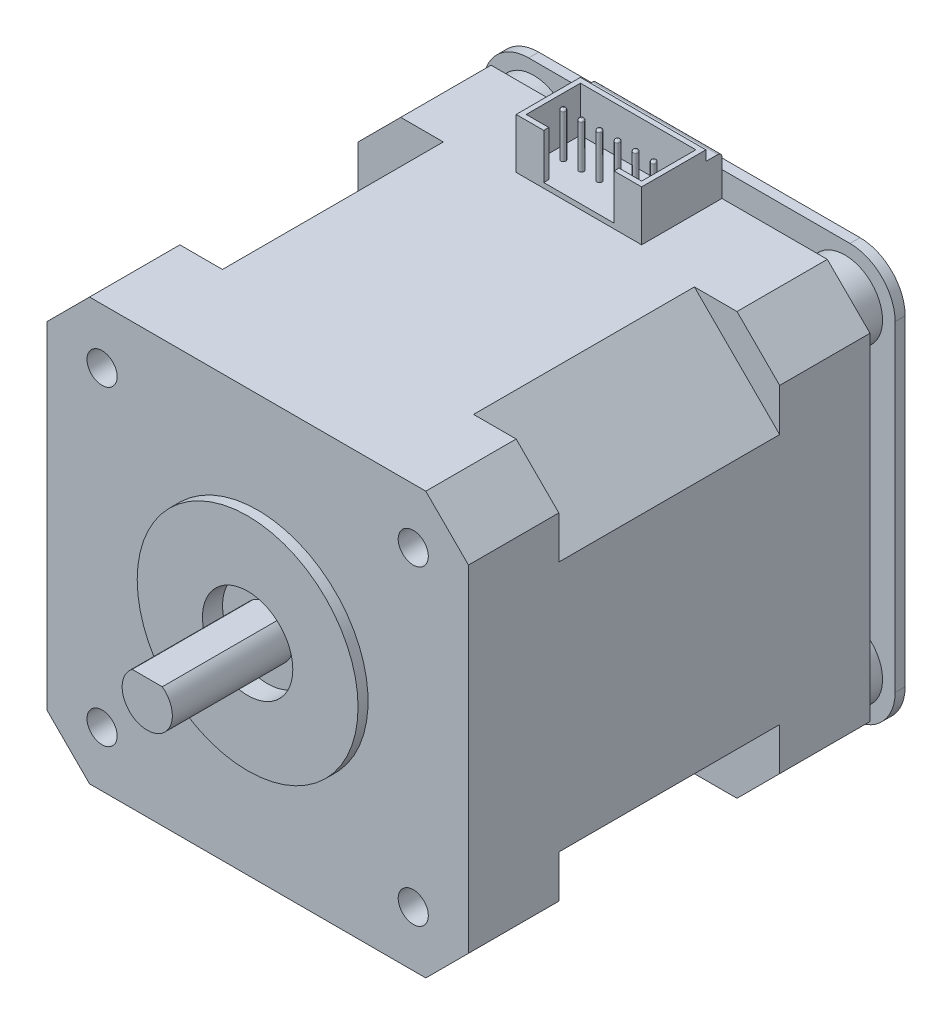
SolidWorks part; units mm, degrees
ref_plane "前视基准面" through (0, 0, 0) normal (0, 0, 1) x (1, 0, 0)
ref_plane "上视基准面" through (0, 0, 0) normal (0, 1, 0) x (1, 0, 0)
ref_plane "右视基准面" through (0, 0, 0) normal (1, 0, 0) x (0, 0, -1)
other "Configuration Table"
sketch "草图1" plane through (0, 0, 0) normal (0, 0, 1) x (1, 0, 0)
  line L0 (0, 0) -> (0, 21) construction
  line L1 (21, 16.75) -> (21, -16.75)
  line L2 (-16.75, 21) -> (16.75, 21)
  line L3 (16.75, -21) -> (-16.75, -21)
  line L4 (-21, -16.75) -> (-21, 16.75)
  line L5 (16.75, 21) -> (21, 16.75)
  line L6 (21, -16.75) -> (16.75, -21)
  line L7 (-16.75, -21) -> (-21, -16.75)
  line L8 (-21, 16.75) -> (-16.75, 21)
  point P2 (0, 0)
  point P3 (0, 21)
  point P4 (0, 0)
  point P10 (-16.7329, -21.7575)
  point P15 (0, 0)
  dimension "D1" = 21
  dimension "D2" = 33.5
  dimension "D3" = 4
extrude "凸台-拉伸1" add sketch "草图1" along normal mid plane 40 contours L2 L5 L1 L6 L3 L7 L4 L8
sketch "草图3" plane through (0, 0, 20) normal (0, 0, 1) x (1, 0, 0)
  circle A0 centre (0, 0) radius 11
  dimension "D1" = 22
extrude "凸台-拉伸2" add sketch "草图3" along normal mid plane 2
sketch "草图4" plane through (0, 0, 21) normal (0, 0, 1) x (1, 0, 0)
  circle A0 centre (0, 0) radius 4.5
  dimension "D1" = 9
extrude "切除-拉伸1" cut sketch "草图4" against normal blind 2
sketch "草图5" plane through (0, 0, 19) normal (0, 0, 1) x (1, 0, 0)
  circle A0 centre (0, 0) radius 2.5
  dimension "D1" = 5
extrude "凸台-拉伸3" add sketch "草图5" along normal mid plane 24
sketch "草图6" plane through (0, 0, 31) normal (0, 0, 1) x (1, 0, 0)
  line L0 (0, 0) -> (0, 2) construction
  line L1 (-1.5, 2) -> (1.5, 2)
  circle A0 centre (0, 0) radius 2.5 construction
  circle A1 centre (0, 0) radius 2.5
  arc A2 (1.5, 2) -> (-1.5, 2) centre (0, 0) ccw
  point P8 (0, 2)
  dimension "D1" = 2
  dimension "D2" = 0
extrude "切除-拉伸2" cut sketch "草图6" against normal blind 24
sketch "草图7" plane through (0, 0, -20) normal (0, 0, -1) x (-1, 0, 0)
  circle A0 centre (0, 0) radius 3
  dimension "D1" = 6
extrude "切除-拉伸3" cut sketch "草图7" against normal blind 2
sketch "草图8" plane through (0, 0, -18) normal (0, 0, -1) x (-1, 0, 0)
  circle A0 centre (0, 0) radius 1.75
  point P2 (0, 0)
  dimension "D1" = 3.5
extrude "凸台-拉伸4" add sketch "草图8" along normal blind 1
sketch "草图9" plane through (0, 0, 20) normal (0, 0, 1) x (1, 0, 0)
  line L0 (0, 0) -> (15.5, 0) construction
  line L1 (15.5, 0) -> (15.5, 15.5) construction
  circle A0 centre (15.5, 15.5) radius 1.5
  circle A1 centre (15.5, -15.5) radius 1.5
  circle A2 centre (-15.5, -15.5) radius 1.5
  circle A3 centre (-15.5, 15.5) radius 1.5
  point P5 (0, 0)
  point P6 (15.5, -15.5)
  point P14 (0, 0)
  dimension "D3" = 3
  dimension "D1" = 15.5
  dimension "D2" = 15.5
  dimension "D4" = 4
extrude "切除-拉伸4" cut sketch "草图9" against normal blind 5
sketch "草图12" plane through (0, 0, -20) normal (0, 0, -1) x (-1, 0, 0)
  line L0 (0, 0) -> (15.5, 0) construction
  line L1 (15.5, 0) -> (15.5, 15.5) construction
  circle A0 centre (15.5, 15.5) radius 3.75
  circle A1 centre (15.5, -15.5) radius 3.75
  circle A2 centre (-15.5, -15.5) radius 3.75
  circle A3 centre (-15.5, 15.5) radius 3.75
  point P5 (-20.6289, 13.0033)
  point P6 (0, 0)
  point P14 (0, 0)
  dimension "D3" = 7.5
  dimension "D1" = 15.5
  dimension "D2" = 15.5
  dimension "D4" = 4
ref_plane "基准面2" through (16.7537, 16.7537, 0) normal (0.7071, 0.7071, 0) x (0.7071, -0.7071, 0)
sketch "草图13" plane through (16.7537, 16.7537, 0) normal (0.7071, 0.7071, 0) x (0.7071, -0.7071, 0)
  line L0 (0, 11) -> (0, -11) construction
  line L1 (-8, -11) -> (8, -11)
  line L2 (-8, 11) -> (8, 11)
  line L3 (-8, 11) -> (-8, -11)
  line L4 (8, 11) -> (8, -11)
  point P2 (0, 0)
  point P8 (0, 11)
  point P9 (0, -11)
  dimension "D1" = 22
  dimension "D2" = 16
  dimension "D3" = 16
extrude "切除-拉伸5" cut sketch "草图13" along normal through all
ref_axis "基准轴1" through (0, 0, 0) along (0, 0, 1)
pattern_circular "阵列(圆周)1" count 4 over 360 about axis through (0, 0, 0) along (0, 0, 1) of "切除-拉伸5"
extrude "凸台-拉伸5" add sketch "草图12" along normal blind 3
sketch "草图15" plane through (0, 0, -20) normal (0, 0, -1) x (-1, 0, 0)
  line L0 (0, 20.5) -> (0, -20.5) construction
  line L1 (20.5, 0) -> (-20.5, 0) construction
  line L2 (-16, 20.5) -> (16, 20.5)
  line L3 (-16, -20.5) -> (16, -20.5)
  line L4 (20.5, 16) -> (20.5, -16)
  line L5 (-20.5, 16) -> (-20.5, -16)
  arc A0 (-20.5, 16) -> (-16, 20.5) centre (-16, 16) cw
  arc A1 (16, 20.5) -> (20.5, 16) centre (16, 16) cw
  arc A2 (20.5, -16) -> (16, -20.5) centre (16, -16) cw
  arc A3 (-16, -20.5) -> (-20.5, -16) centre (-16, -16) cw
  point P2 (0, 0)
  point P4 (0, 0)
  point P5 (0, 0)
  point P16 (20.5, 0)
  point P17 (-20.5, 0)
  point P24 (0, 20.5)
  point P25 (0, -20.5)
  dimension "D1" = 41
  dimension "D2" = 41
  dimension "D3" = 32
  dimension "D4" = 32
extrude "凸台-拉伸6" add sketch "草图15" along normal blind 1 from offset 3
sketch "草图17" plane through (0, 21, 0) normal (0, 1, 0) x (1, 0, 0)
  line L1 (0, 0) -> (0, 20) construction
  line L2 (-16.75, 20) -> (16.75, 20) construction
  line L3 (-6.25, 20) -> (6.25, 20)
  line L4 (-6.25, 12) -> (6.25, 12)
  line L5 (6.25, 12) -> (6.25, 20)
  line L6 (-6.25, 12) -> (-6.25, 20)
  point P7 (0, 20)
  point P10 (0, 12)
  dimension "D1" = 12.5
  dimension "D2" = 8
extrude "凸台-拉伸7" add sketch "草图17" along normal blind 5
sketch "草图20" plane through (6.25, 0, 0) normal (1, 0, 0) x (0, 0, -1)
  line L0 (20, 26) -> (20, 21) construction
  line L1 (12, 26) -> (20, 26) construction
  line L2 (20, 26) -> (20, 25)
  line L3 (18.4, 26) -> (20, 26)
  line L12 (18.4, 26) -> (18.4, 25)
  line L13 (18.4, 25) -> (20, 25)
  dimension "D1" = 1
  dimension "D2" = 1.6
extrude "切除-拉伸6" cut sketch "草图20" against normal through all
fillet "圆角1" radius 0.4 1 edges at (0, 25, -20)
sketch "草图21" plane through (0, 26, 0) normal (0, 1, 0) x (1, 0, 0)
  line L0 (-6.25, 12) -> (6.25, 12) construction
  line L1 (-6.25, 12) -> (6.25, 12) construction
  line L2 (-5.75, 17.9) -> (5.75, 17.9)
  line L3 (0, 12) -> (0, 17.9) construction
  line L4 (-5.75, 12.5) -> (5.75, 12.5)
  line L6 (5.75, 17.9) -> (5.75, 12.5)
  line L8 (-5.75, 17.9) -> (-5.75, 12.5)
  point P8 (0, 12.5)
  dimension "D1" = 5.9
  dimension "D2" = 11.5
  dimension "D3" = 5.4
extrude "切除-拉伸7" cut sketch "草图21" against normal blind 4.5
sketch "草图22" plane through (0, 26, 0) normal (0, 1, 0) x (1, 0, 0)
  line L0 (-5.75, 12.5) -> (5.75, 12.5) construction
  line L1 (-5.75, 12.5) -> (5.75, 12.5) construction
  line L2 (-3.5, 12.5) -> (-3.5, 12)
  line L3 (-6.25, 12) -> (6.25, 12) construction
  line L4 (0, 12.5) -> (0, 12) construction
  line L5 (3.5, 12.5) -> (3.5, 12)
  line L6 (-6.25, 12) -> (6.25, 12) construction
  line L7 (3.5, 12.5) -> (-3.5, 12.5)
  line L8 (-3.5, 12) -> (3.5, 12)
  dimension "D1" = 3.5
  dimension "D2" = 3.5
extrude "切除-拉伸8" cut sketch "草图22" against normal blind 4.5
sketch "草图23" plane through (0, 0, -24) normal (0, 0, -1) x (-1, 0, 0)
  line L0 (20.5, -16) -> (20.5, 16) construction
  line L1 (20.5, -16) -> (20.5, 16) construction
  line L2 (20.5, 0) -> (14.5, 0) construction
  line L3 (14.5, 11.35) -> (14.5, -11.35)
  line L4 (24.5, 11.35) -> (24.5, -11.35)
  line L5 (14.5, 11.35) -> (24.5, 11.35)
  line L6 (24.5, -11.35) -> (14.5, -11.35)
  point P7 (14.5, 0)
  point P10 (24.5, 0)
  dimension "D1" = 6
  dimension "D2" = 22.7
  dimension "D3" = 4
extrude "凸台-拉伸8" add sketch "草图23" along normal blind 6.5
sketch "草图24" plane through (-24.5, 0, 0) normal (-1, 0, 0) x (0, 0, 1)
  line L0 (-30, 10.85) -> (-30, -10.85)
  line L1 (-30.5, 0) -> (-24.3219, 0) construction
  line L2 (-24.5, 10.85) -> (-24.5, -10.85)
  line L3 (-30, 10.85) -> (-24.5, 10.85)
  line L4 (-24, -11.35) -> (-24, 11.35)
  line L5 (-24, 11.35) -> (-30.5, 11.35)
  line L6 (-30.5, 11.35) -> (-30.5, -11.35)
  line L7 (-30.5, -11.35) -> (-24, -11.35)
  line L10 (-30.5, 11.35) -> (-30.5, -11.35) construction
  line L12 (-30, -10.85) -> (-24.5, -10.85)
  point P11 (-24.5, 0)
  point P12 (-30, 0)
  dimension "D2" = 0.5
  dimension "D3" = 21.7
  dimension "D4" = 5.5
  dimension "D1" = 0
extrude "切除-拉伸9" cut sketch "草图24" against normal blind 8
sketch "草图25" plane through (-24.5, 0, 0) normal (-1, 0, 0) x (0, 0, 1)
  line L0 (-30.5, -11.35) -> (-30.5, 11.35) construction
  line L1 (-30.5, -11.35) -> (-30.5, 11.35) construction
  line L2 (-30.5, 0) -> (-30, 0) construction
  line L3 (-30, 10.85) -> (-30, -10.85) construction
  line L4 (-30, 6.5) -> (-30, -6.5)
  line L5 (-30.5, 6.5) -> (-30.5, -6.5)
  line L6 (-30.5, 6.5) -> (-30, 6.5)
  line L7 (-30, -6.5) -> (-30.5, -6.5)
  point P10 (-30.5, 0)
  point P11 (-30, 0)
  dimension "D1" = 13
extrude "切除-拉伸10" cut sketch "草图25" against normal blind 8
sketch "草图26" plane through (-16.5, 0, 0) normal (-1, 0, 0) x (0, 0, 1)
  line L1 (-30.5, 6.5) -> (-30.5, -6.5) construction
  line L2 (-30.5, 0) -> (-24.5, 0) construction
  line L3 (-24.5, -10.85) -> (-24.5, 10.85) construction
  line L4 (-27.5, 4.3514) -> (-27.5, -4.3514) construction
  circle A0 centre (-27.5, 6.5) radius 0.25
  circle A1 centre (-27.5, 3.9) radius 0.25
  circle A2 centre (-27.5, 1.3) radius 0.25
  circle A3 centre (-27.5, 9.1) radius 0.25
  circle A4 centre (-27.5, -1.3) radius 0.25
  circle A5 centre (-27.5, -3.9) radius 0.25
  circle A6 centre (-27.5, -6.5) radius 0.25
  circle A7 centre (-27.5, -9.1) radius 0.25
  point P8 (-27.5, 0)
  point P9 (-27.5, 0)
  dimension "D1" = 0.5
  dimension "D3" = 0.5
  dimension "D5" = 0.5
  dimension "D7" = 0.5
  dimension "D2" = 6.5
  dimension "D4" = 3.9
  dimension "D6" = 1.3
  dimension "D8" = 9.1
extrude "凸台-拉伸10" add sketch "草图26" along normal blind 8
sketch "草图27" plane through (0, 21.5, 0) normal (0, 1, 0) x (1, 0, 0)
  line L0 (0, 17.9) -> (0, 12) construction
  line L1 (5.75, 17.9) -> (-5.75, 17.9) construction
  line L2 (-6.25, 12) -> (6.25, 12) construction
  line L3 (-2.9533, 14.95) -> (2.9533, 14.95) construction
  circle A0 centre (0.9, 14.95) radius 0.25
  circle A1 centre (2.7, 14.95) radius 0.25
  circle A2 centre (4.5, 14.95) radius 0.25
  circle A3 centre (-4.5, 14.95) radius 0.25
  circle A4 centre (-2.7, 14.95) radius 0.25
  circle A5 centre (-0.9, 14.95) radius 0.25
  point P8 (0, 14.95)
  point P9 (0, 14.95)
  dimension "D1" = 0.5
  dimension "D2" = 0.5
  dimension "D3" = 0.5
  dimension "D4" = 0.9
  dimension "D5" = 2.7
  dimension "D6" = 4.5
extrude "凸台-拉伸11" add sketch "草图27" along normal blind 4.5
fillet "圆角2" radius 0.2 8 edges at (-24.5, -9.1, -27.75) (-24.5, -6.5, -27.75) (-24.5, -3.9, -27.75) (-24.5, -1.3, -27.75) (-24.5, 1.3, -27.25) (-24.5, 3.9, -27.25) (-24.5, 6.5, -27.25) (-24.5, 9.1, -27.25)
fillet "圆角3" radius 0.2 6 edges at (-4.5, 26, -15.2) (-2.7, 26, -15.2) (-0.9, 26, -15.2) (0.9, 26, -14.7) (2.7, 26, -14.7) (4.5, 26, -14.7)
